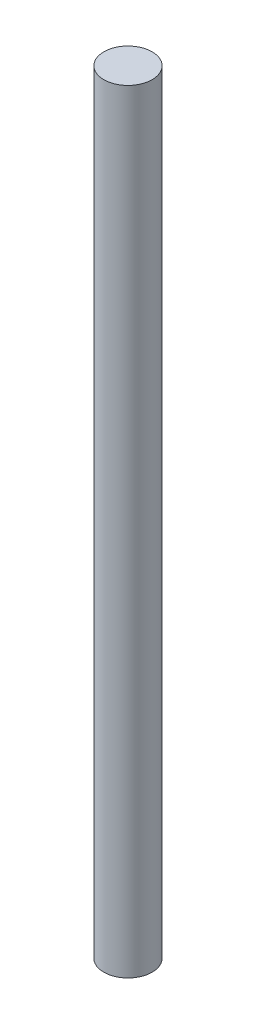
SolidWorks part; units mm, degrees
ref_plane "Front Plane" through (0, 0, 0) normal (0, 0, 1) x (1, 0, 0)
ref_plane "Top Plane" through (0, 0, 0) normal (0, 1, 0) x (1, 0, 0)
ref_plane "Right Plane" through (0, 0, 0) normal (1, 0, 0) x (0, 0, -1)
sketch "Sketch1" plane through (0, 0, 0) normal (0, 1, 0) x (1, 0, 0)
  circle A0 centre (0, 0) radius 3.175
  dimension "D1" = 6.35
extrude "Boss-Extrude1" add sketch "Sketch1" along normal blind 50.8 and the other way blind 50.8
ref_axis "Axis1" through (0, -50.8, 0) along (0, 1, 0)
